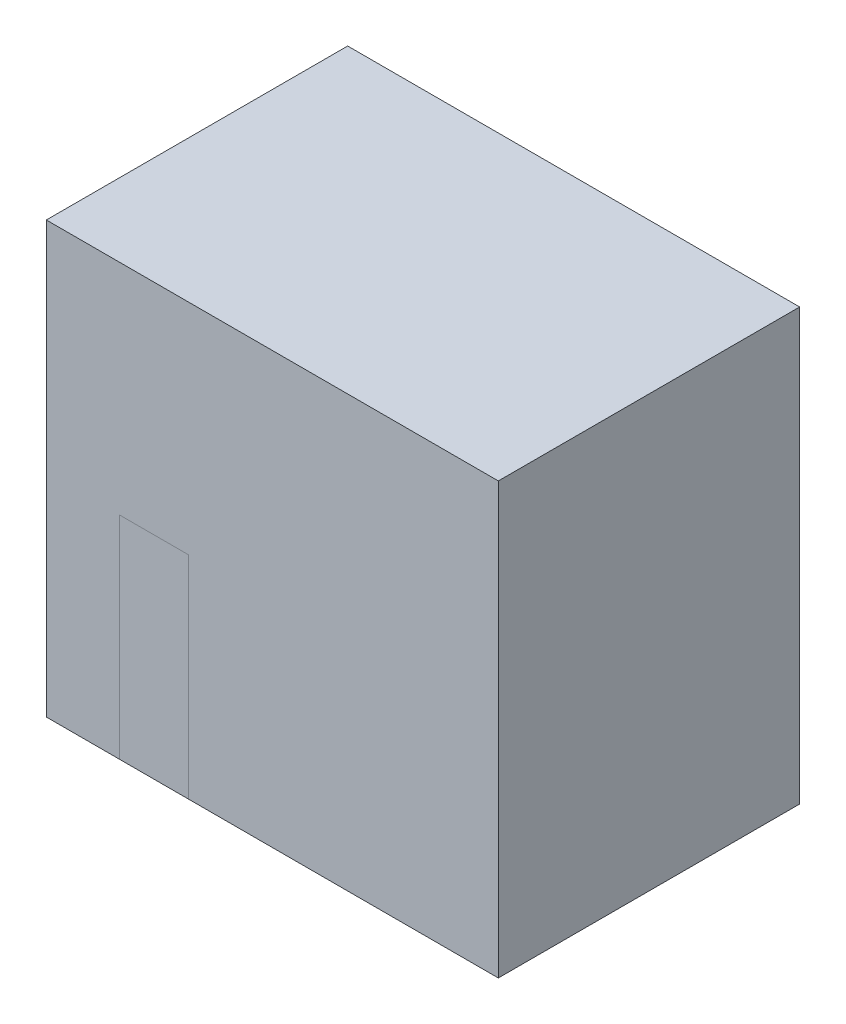
SolidWorks part; units mm, degrees
other "rotor"
other "fluid_domain"
other "sma_pocket"
other "louver_4"
other "louver_3"
other "louver_2"
other "louver_1"
other "duct_wall"
ref_plane "Front Plane" through (0, 0, 0) normal (0, 0, 1) x (1, 0, 0)
ref_plane "Top Plane" through (0, 0, 0) normal (0, 1, 0) x (1, 0, 0)
ref_plane "Right Plane" through (0, 0, 0) normal (1, 0, 0) x (0, 0, -1)
other "Configuration Table"
sketch "Sketch1" plane through (0, 0, 0) normal (1, 0, 0) x (0, 0, -1)
  line L1 (70, 50) -> (-70, 50)
  line L2 (70, 50) -> (70, 250)
  line L3 (70, 250) -> (-70, 250)
  line L4 (-70, 50) -> (-70, 250)
  line L5 (70, 50) -> (-70, 250) construction
  line L6 (70, 250) -> (-70, 50) construction
  point P0 (0, 150)
extrude "fluid_box" add sketch "Sketch1" along normal blind 210 from offset 50 separate body offset against normal yes
sketch "Sketch2" plane through (0, 0, 0) normal (1, 0, 0) x (0, 0, -1)
  line L0 (70, 50) -> (-70, 50)
  line L1 (-70, 50) -> (-70, 148.3105)
  line L2 (70, 148.3105) -> (70, 50)
  arc A0 (-70, 148.3105) -> (70, 148.3105) centre (0, 0) cw
extrude "rotor_tool" add sketch "Sketch2" along normal mid plane 32 separate body
sketch "Sketch3" plane through (0, 0, 0) normal (1, 0, 0) x (0, 0, -1)
  line L1 (32, 88) -> (-32, 88)
  line L2 (32, 88) -> (32, 192)
  line L3 (32, 192) -> (-32, 192)
  line L4 (-32, 88) -> (-32, 192)
  line L5 (32, 88) -> (-32, 192) construction
  line L6 (32, 192) -> (-32, 88) construction
  line L7 (30.5579, 90.3433) -> (-30.5579, 90.3433)
  line L8 (30.5579, 90.3433) -> (30.5579, 189.6567)
  line L9 (30.5579, 189.6567) -> (-30.5579, 189.6567)
  line L10 (-30.5579, 90.3433) -> (-30.5579, 189.6567)
  line L11 (30.5579, 90.3433) -> (-30.5579, 189.6567) construction
  line L12 (30.5579, 189.6567) -> (-30.5579, 90.3433) construction
  point P0 (0, 140)
  point P5 (0, 140)
extrude "duct_tool" add sketch "Sketch3" along normal blind 80 from offset 18 separate body
sketch "Sketch4" plane through (0, 0, 0) normal (1, 0, 0) x (0, 0, -1)
  line L1 (28, 101) -> (-28, 101)
  line L2 (28, 101) -> (28, 119)
  line L3 (28, 119) -> (-28, 119)
  line L4 (-28, 101) -> (-28, 119)
  line L5 (28, 101) -> (-28, 119) construction
  line L6 (28, 119) -> (-28, 101) construction
  point P0 (0, 110)
extrude "louver1_tool" add sketch "Sketch4" along normal blind 2 from offset 57 separate body
sketch "Sketch5" plane through (0, 0, 0) normal (1, 0, 0) x (0, 0, -1)
  line L1 (28, 121) -> (-28, 121)
  line L2 (28, 121) -> (28, 139)
  line L3 (28, 139) -> (-28, 139)
  line L4 (-28, 121) -> (-28, 139)
  line L5 (28, 121) -> (-28, 139) construction
  line L6 (28, 139) -> (-28, 121) construction
  point P0 (0, 130)
extrude "louver2_tool" add sketch "Sketch5" along normal blind 2 from offset 57 separate body
sketch "Sketch6" plane through (0, 0, 0) normal (1, 0, 0) x (0, 0, -1)
  line L1 (28, 141) -> (-28, 141)
  line L2 (28, 141) -> (28, 159)
  line L3 (28, 159) -> (-28, 159)
  line L4 (-28, 141) -> (-28, 159)
  line L5 (28, 141) -> (-28, 159) construction
  line L6 (28, 159) -> (-28, 141) construction
  point P0 (0, 150)
extrude "louver3_tool" add sketch "Sketch6" along normal blind 2 from offset 57 separate body
sketch "Sketch7" plane through (0, 0, 0) normal (1, 0, 0) x (0, 0, -1)
  line L1 (28, 161) -> (-28, 161)
  line L2 (28, 161) -> (28, 179)
  line L3 (28, 179) -> (-28, 179)
  line L4 (-28, 161) -> (-28, 179)
  line L5 (28, 161) -> (-28, 179) construction
  line L6 (28, 179) -> (-28, 161) construction
  point P0 (0, 170)
extrude "louver4_tool" add sketch "Sketch7" along normal blind 2 from offset 57 separate body
sketch "Sketch8" plane through (0, 0, 0) normal (1, 0, 0) x (0, 0, -1)
  line L1 (-32, 176) -> (-45, 176)
  line L2 (-32, 176) -> (-32, 205)
  line L3 (-32, 205) -> (-45, 205)
  line L4 (-45, 176) -> (-45, 205)
  line L5 (-32, 176) -> (-45, 205) construction
  line L6 (-32, 205) -> (-45, 176) construction
  point P0 (-38.5, 190.5)
extrude "pocket_tool" add sketch "Sketch8" along normal blind 17 from offset 58 separate body
combine bodies "Combine1" operation type subtract main body 102 bodies to subtract 106 109 104 108 107 103 105
sketch "Sketch9" plane through (0, 0, 0) normal (1, 0, 0) x (0, 0, -1)
  line L0 (70, 50) -> (-70, 50)
  line L1 (-70, 50) -> (-70, 148.3105)
  line L2 (70, 148.3105) -> (70, 50)
  arc A0 (-70, 148.3105) -> (70, 148.3105) centre (0, 0) cw
extrude "rotor_keep" add sketch "Sketch9" along normal mid plane 32 separate body
sketch "Sketch10" plane through (0, 0, 0) normal (1, 0, 0) x (0, 0, -1)
  line L1 (32, 88) -> (-32, 88)
  line L2 (32, 88) -> (32, 192)
  line L3 (32, 192) -> (-32, 192)
  line L4 (-32, 88) -> (-32, 192)
  line L5 (32, 88) -> (-32, 192) construction
  line L6 (32, 192) -> (-32, 88) construction
  line L7 (30.5579, 90.3433) -> (-30.5579, 90.3433)
  line L8 (30.5579, 90.3433) -> (30.5579, 189.6567)
  line L9 (30.5579, 189.6567) -> (-30.5579, 189.6567)
  line L10 (-30.5579, 90.3433) -> (-30.5579, 189.6567)
  line L11 (30.5579, 90.3433) -> (-30.5579, 189.6567) construction
  line L12 (30.5579, 189.6567) -> (-30.5579, 90.3433) construction
  point P0 (0, 140)
  point P5 (0, 140)
extrude "duct_keep" add sketch "Sketch10" along normal blind 80 from offset 18 separate body
sketch "Sketch11" plane through (0, 0, 0) normal (1, 0, 0) x (0, 0, -1)
  line L1 (28, 101) -> (-28, 101)
  line L2 (28, 101) -> (28, 119)
  line L3 (28, 119) -> (-28, 119)
  line L4 (-28, 101) -> (-28, 119)
  line L5 (28, 101) -> (-28, 119) construction
  line L6 (28, 119) -> (-28, 101) construction
  point P0 (0, 110)
extrude "louver1_keep" add sketch "Sketch11" along normal blind 2 from offset 57 separate body
sketch "Sketch12" plane through (0, 0, 0) normal (1, 0, 0) x (0, 0, -1)
  line L1 (28, 121) -> (-28, 121)
  line L2 (28, 121) -> (28, 139)
  line L3 (28, 139) -> (-28, 139)
  line L4 (-28, 121) -> (-28, 139)
  line L5 (28, 121) -> (-28, 139) construction
  line L6 (28, 139) -> (-28, 121) construction
  point P0 (0, 130)
extrude "louver2_keep" add sketch "Sketch12" along normal blind 2 from offset 57 separate body
sketch "Sketch13" plane through (0, 0, 0) normal (1, 0, 0) x (0, 0, -1)
  line L1 (28, 141) -> (-28, 141)
  line L2 (28, 141) -> (28, 159)
  line L3 (28, 159) -> (-28, 159)
  line L4 (-28, 141) -> (-28, 159)
  line L5 (28, 141) -> (-28, 159) construction
  line L6 (28, 159) -> (-28, 141) construction
  point P0 (0, 150)
extrude "louver3_keep" add sketch "Sketch13" along normal blind 2 from offset 57 separate body
sketch "Sketch14" plane through (0, 0, 0) normal (1, 0, 0) x (0, 0, -1)
  line L1 (28, 161) -> (-28, 161)
  line L2 (28, 161) -> (28, 179)
  line L3 (28, 179) -> (-28, 179)
  line L4 (-28, 161) -> (-28, 179)
  line L5 (28, 161) -> (-28, 179) construction
  line L6 (28, 179) -> (-28, 161) construction
  point P0 (0, 170)
extrude "louver4_keep" add sketch "Sketch14" along normal blind 2 from offset 57 separate body
sketch "Sketch15" plane through (0, 0, 0) normal (1, 0, 0) x (0, 0, -1)
  line L1 (-32, 176) -> (-45, 176)
  line L2 (-32, 176) -> (-32, 205)
  line L3 (-32, 205) -> (-45, 205)
  line L4 (-45, 176) -> (-45, 205)
  line L5 (-32, 176) -> (-45, 205) construction
  line L6 (-32, 205) -> (-45, 176) construction
  point P0 (-38.5, 190.5)
extrude "pocket_keep" add sketch "Sketch15" along normal blind 17 from offset 58 separate body
